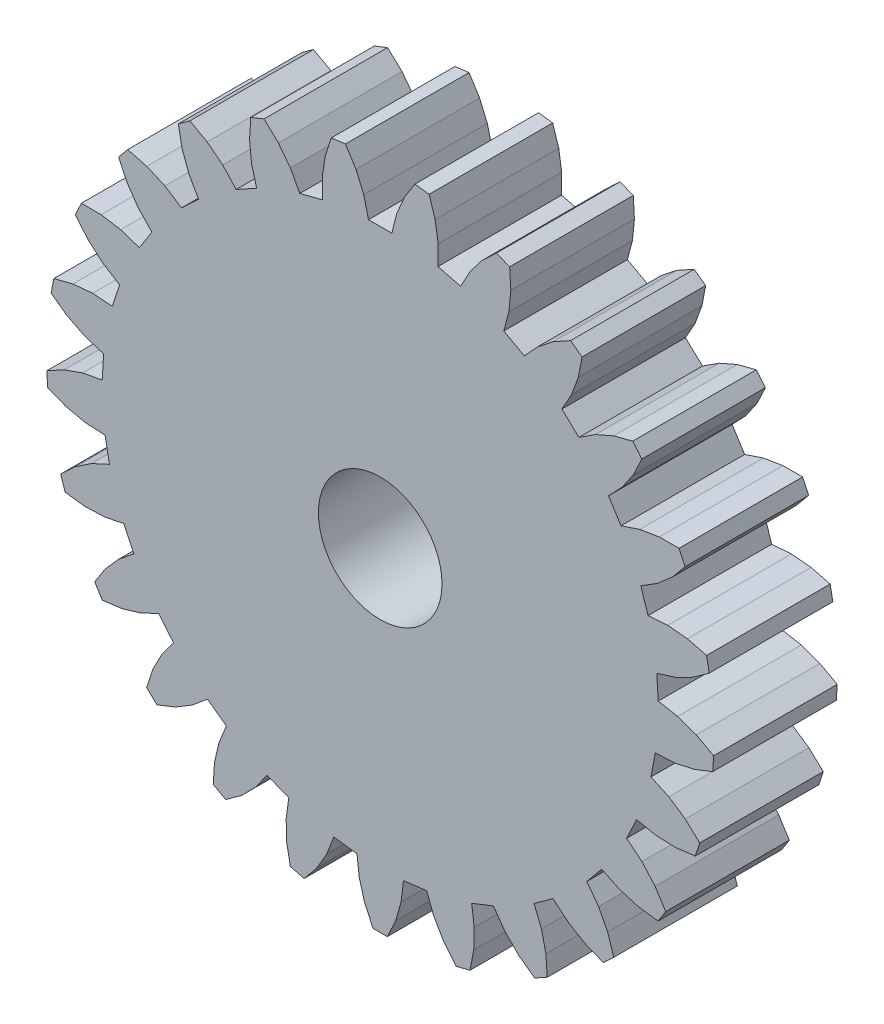
SolidWorks part; units mm, degrees
ref_plane "Front Plane" through (0, 0, 0) normal (0, 0, 1) x (1, 0, 0)
ref_plane "Top Plane" through (0, 0, 0) normal (0, 1, 0) x (1, 0, 0)
ref_plane "Right Plane" through (0, 0, 0) normal (1, 0, 0) x (0, 0, -1)
sketch "Sketch3" plane through (0, 0, 0) normal (0, 0, 1) x (1, 0, 0)
  line L0 (-2.8117, 26.9235) -> (-3.9548, 26.7791)
  line L1 (-3.9548, 26.7791) -> (-4.4453, 25.2575)
  line L2 (-4.4453, 25.2575) -> (-4.6871, 23.6772)
  line L3 (-4.6871, 23.6772) -> (-4.6739, 22.0785)
  line L5 (-0.9462, 22.5494) -> (-1.331, 24.1011)
  line L6 (-1.331, 24.1011) -> (-1.9582, 25.5717)
  line L7 (-1.9582, 25.5717) -> (-2.8117, 26.9235)
  line L8 (-9.4015, 25.3807) -> (-10.4728, 24.9565)
  line L9 (-10.4728, 24.9565) -> (-10.5694, 23.3607)
  line L10 (-10.5694, 23.3607) -> (-10.4106, 21.7699)
  line L11 (-10.4106, 21.7699) -> (-10.0003, 20.2247)
  line L13 (-6.5068, 21.6079) -> (-7.2654, 23.0152)
  line L14 (-7.2654, 23.0152) -> (-8.2386, 24.2836)
  line L15 (-8.2386, 24.2836) -> (-9.4015, 25.3807)
  line L16 (-15.4005, 22.2474) -> (-16.3327, 21.5702)
  line L17 (-16.3327, 21.5702) -> (-16.0295, 20.0005)
  line L18 (-16.0295, 20.0005) -> (-15.48, 18.4992)
  line L19 (-15.48, 18.4992) -> (-14.6983, 17.1046)
  line L21 (-11.6585, 19.3131) -> (-12.7433, 20.4875)
  line L22 (-12.7433, 20.4875) -> (-14.0013, 21.474)
  line L23 (-14.0013, 21.474) -> (-15.4005, 22.2474)
  line L24 (-16.0777, 15.8092) -> (-17.4205, 16.6769)
  line L25 (-17.4205, 16.6769) -> (-18.8844, 17.3196)
  line L26 (-18.8844, 17.3196) -> (-20.4319, 17.7207)
  line L27 (-20.4319, 17.7207) -> (-21.1663, 16.833)
  line L28 (-21.1663, 16.833) -> (-20.4823, 15.388)
  line L29 (-20.4823, 15.388) -> (-19.5767, 14.0705)
  line L30 (-19.5767, 14.0705) -> (-18.4728, 12.9141)
  line L32 (-19.4867, 11.3164) -> (-21.0031, 11.8229)
  line L33 (-21.0031, 11.8229) -> (-22.5808, 12.0813)
  line L34 (-22.5808, 12.0813) -> (-24.1795, 12.085)
  line L35 (-24.1795, 12.085) -> (-24.6701, 11.0425)
  line L36 (-24.6701, 11.0425) -> (-23.6482, 9.813)
  line L37 (-23.6482, 9.813) -> (-22.4434, 8.7621)
  line L38 (-22.4434, 8.7621) -> (-21.0865, 7.9166)
  line L40 (-21.6713, 6.1169) -> (-23.266, 6.2304)
  line L41 (-23.266, 6.2304) -> (-24.8584, 6.0884)
  line L42 (-24.8584, 6.0884) -> (-26.4078, 5.6944)
  line L43 (-26.4078, 5.6944) -> (-26.6237, 4.5626)
  line L44 (-26.6237, 4.5626) -> (-25.3281, 3.6259)
  line L45 (-25.3281, 3.6259) -> (-23.8998, 2.9076)
  line L46 (-23.8998, 2.9076) -> (-22.3754, 2.4261)
  line L48 (-22.4942, 0.5375) -> (-24.067, 0.2509)
  line L49 (-24.067, 0.2509) -> (-25.574, -0.2827)
  line L50 (-25.574, -0.2827) -> (-26.9768, -1.0497)
  line L51 (-26.9768, -1.0497) -> (-26.9044, -2.1996)
  line L52 (-26.9044, -2.1996) -> (-25.4166, -2.7847)
  line L53 (-25.4166, -2.7847) -> (-23.8546, -3.1252)
  line L54 (-23.8546, -3.1252) -> (-22.2582, -3.2124)
  line L56 (-21.9036, -5.0712) -> (-23.3558, -5.74)
  line L57 (-23.3558, -5.74) -> (-24.6828, -6.6316)
  line L58 (-24.6828, -6.6316) -> (-25.8507, -7.7233)
  line L59 (-25.8507, -7.7233) -> (-25.4947, -8.8191)
  line L60 (-25.4947, -8.8191) -> (-23.9081, -9.0158)
  line L61 (-23.9081, -9.0158) -> (-22.3104, -8.9572)
  line L62 (-22.3104, -8.9572) -> (-20.7426, -8.6447)
  line L64 (-19.9368, -10.3569) -> (-21.177, -11.3658)
  line L65 (-21.177, -11.3658) -> (-22.2406, -12.5594)
  line L66 (-22.2406, -12.5594) -> (-23.1004, -13.9073)
  line L67 (-23.1004, -13.9073) -> (-22.483, -14.8801)
  line L68 (-22.483, -14.8801) -> (-20.8973, -14.6761)
  line L69 (-20.8973, -14.6761) -> (-19.3645, -14.222)
  line L70 (-19.3645, -14.222) -> (-17.9236, -13.5294)
  line L72 (-16.7174, -14.9874) -> (-17.6677, -16.273)
  line L73 (-17.6677, -16.273) -> (-18.401, -17.6937)
  line L74 (-18.401, -17.6937) -> (-18.8985, -19.213)
  line L75 (-18.8985, -19.213) -> (-18.0586, -20.0017)
  line L76 (-18.0586, -20.0017) -> (-16.5735, -19.4098)
  line L77 (-16.5735, -19.4098) -> (-15.2017, -18.5887)
  line L78 (-15.2017, -18.5887) -> (-13.9783, -17.5595)
  line L80 (-12.4474, -18.6718) -> (-13.0482, -20.1533)
  line L81 (-13.0482, -20.1533) -> (-13.4052, -21.7117)
  line L82 (-13.4052, -21.7117) -> (-13.5092, -23.307)
  line L83 (-13.5092, -23.307) -> (-12.4996, -23.8621)
  line L84 (-12.4996, -23.8621) -> (-11.2083, -22.9194)
  line L85 (-11.2083, -22.9194) -> (-10.0838, -21.783)
  line L86 (-10.0838, -21.783) -> (-9.1548, -20.4819)
  line L88 (-7.3954, -21.1785) -> (-7.6088, -22.7629)
  line L89 (-7.6088, -22.7629) -> (-7.5671, -24.3611)
  line L90 (-7.5671, -24.3611) -> (-7.2711, -25.9322)
  line L91 (-7.2711, -25.9322) -> (-6.1551, -26.2187)
  line L92 (-6.1551, -26.2187) -> (-5.1389, -24.9846)
  line L93 (-5.1389, -24.9846) -> (-4.3324, -23.6042)
  line L94 (-4.3324, -23.6042) -> (-3.7561, -22.1129)
  line L96 (-1.8787, -22.3501) -> (-1.6914, -23.9378)
  line L97 (-1.6914, -23.9378) -> (-1.2535, -25.4754)
  line L98 (-1.2535, -25.4754) -> (-0.5761, -26.9235)
  line L99 (-0.5761, -26.9235) -> (0.5761, -26.9235)
  line L100 (0.5761, -26.9235) -> (1.2534, -25.4754)
  line L101 (1.2534, -25.4754) -> (1.6914, -23.9378)
  line L102 (1.6914, -23.9378) -> (1.8787, -22.3501)
  line L104 (3.7561, -22.1129) -> (4.3323, -23.6042)
  line L105 (4.3323, -23.6042) -> (5.1389, -24.9846)
  line L106 (5.1389, -24.9846) -> (6.1551, -26.2187)
  line L107 (6.1551, -26.2187) -> (7.2711, -25.9322)
  line L108 (7.2711, -25.9322) -> (7.567, -24.3611)
  line L109 (7.567, -24.3611) -> (7.6088, -22.7629)
  line L110 (7.6088, -22.7629) -> (7.3954, -21.1785)
  line L112 (9.1548, -20.4819) -> (10.0838, -21.783)
  line L113 (10.0838, -21.783) -> (11.2083, -22.9194)
  line L114 (11.2083, -22.9194) -> (12.4995, -23.8621)
  line L115 (12.4995, -23.8621) -> (13.5092, -23.307)
  line L116 (13.5092, -23.307) -> (13.4051, -21.7117)
  line L117 (13.4051, -21.7117) -> (13.0482, -20.1533)
  line L118 (13.0482, -20.1533) -> (12.4474, -18.6718)
  line L120 (13.9783, -17.5595) -> (15.2017, -18.5887)
  line L121 (15.2017, -18.5887) -> (16.5735, -19.4098)
  line L122 (16.5735, -19.4098) -> (18.0586, -20.0017)
  line L123 (18.0586, -20.0017) -> (18.8985, -19.213)
  line L124 (18.8985, -19.213) -> (18.401, -17.6937)
  line L125 (18.401, -17.6937) -> (17.6676, -16.273)
  line L126 (17.6676, -16.273) -> (16.7173, -14.9874)
  line L128 (17.9235, -13.5294) -> (19.3645, -14.222)
  line L129 (19.3645, -14.222) -> (20.8973, -14.6761)
  line L130 (20.8973, -14.6761) -> (22.483, -14.8801)
  line L131 (22.483, -14.8801) -> (23.1003, -13.9073)
  line L132 (23.1003, -13.9073) -> (22.2406, -12.5594)
  line L133 (22.2406, -12.5594) -> (21.177, -11.3658)
  line L134 (21.177, -11.3658) -> (19.9368, -10.3569)
  line L136 (20.7425, -8.6447) -> (22.3104, -8.9572)
  line L137 (22.3104, -8.9572) -> (23.9081, -9.0158)
  line L138 (23.9081, -9.0158) -> (25.4946, -8.8191)
  line L139 (25.4946, -8.8191) -> (25.8507, -7.7233)
  line L140 (25.8507, -7.7233) -> (24.6828, -6.6316)
  line L141 (24.6828, -6.6316) -> (23.3558, -5.74)
  line L142 (23.3558, -5.74) -> (21.9036, -5.0712)
  line L144 (22.2582, -3.2124) -> (23.8545, -3.1252)
  line L145 (23.8545, -3.1252) -> (25.4166, -2.7847)
  line L146 (25.4166, -2.7847) -> (26.9044, -2.1996)
  line L147 (26.9044, -2.1996) -> (26.9768, -1.0497)
  line L148 (26.9768, -1.0497) -> (25.574, -0.2827)
  line L149 (25.574, -0.2827) -> (24.067, 0.2509)
  line L150 (24.067, 0.2509) -> (22.4941, 0.5375)
  line L152 (22.3753, 2.4261) -> (23.8998, 2.9076)
  line L153 (23.8998, 2.9076) -> (25.3281, 3.6259)
  line L154 (25.3281, 3.6259) -> (26.6236, 4.5626)
  line L155 (26.6236, 4.5626) -> (26.4078, 5.6944)
  line L156 (26.4078, 5.6944) -> (24.8584, 6.0884)
  line L157 (24.8584, 6.0884) -> (23.2659, 6.2304)
  line L158 (23.2659, 6.2304) -> (21.6712, 6.1169)
  line L160 (21.0865, 7.9166) -> (22.4433, 8.7621)
  line L161 (22.4433, 8.7621) -> (23.6481, 9.813)
  line L162 (23.6481, 9.813) -> (24.6701, 11.0425)
  line L163 (24.6701, 11.0425) -> (24.1795, 12.085)
  line L164 (24.1795, 12.085) -> (22.5807, 12.0813)
  line L165 (22.5807, 12.0813) -> (21.003, 11.8229)
  line L166 (21.003, 11.8229) -> (19.4867, 11.3164)
  line L168 (18.4727, 12.9141) -> (19.5767, 14.0705)
  line L169 (19.5767, 14.0705) -> (20.4823, 15.388)
  line L170 (20.4823, 15.388) -> (21.1663, 16.833)
  line L171 (21.1663, 16.833) -> (20.4319, 17.7207)
  line L172 (20.4319, 17.7207) -> (18.8843, 17.3196)
  line L173 (18.8843, 17.3196) -> (17.4205, 16.6769)
  line L174 (17.4205, 16.6769) -> (16.0777, 15.8092)
  line L176 (18.4727, 12.9141) -> (19.4867, 11.3164)
  line L177 (14.6983, 17.1046) -> (15.48, 18.4992)
  line L178 (15.48, 18.4992) -> (16.0295, 20.0005)
  line L179 (16.0295, 20.0005) -> (16.3327, 21.5702)
  line L180 (16.3327, 21.5702) -> (15.4005, 22.2474)
  line L181 (15.4005, 22.2474) -> (14.0013, 21.474)
  line L182 (14.0013, 21.474) -> (12.7433, 20.4875)
  line L183 (12.7433, 20.4875) -> (11.6585, 19.3131)
  line L185 (10.0003, 20.2247) -> (10.4106, 21.7699)
  line L186 (10.4106, 21.7699) -> (10.5694, 23.3607)
  line L187 (10.5694, 23.3607) -> (10.4727, 24.9565)
  line L188 (10.4727, 24.9565) -> (9.4014, 25.3807)
  line L189 (9.4014, 25.3807) -> (8.2386, 24.2836)
  line L190 (8.2386, 24.2836) -> (7.2654, 23.0152)
  line L191 (7.2654, 23.0152) -> (6.5067, 21.6079)
  line L193 (4.6739, 22.0785) -> (4.6871, 23.6772)
  line L194 (4.6871, 23.6772) -> (4.4453, 25.2575)
  line L195 (4.4453, 25.2575) -> (3.9548, 26.7791)
  line L196 (3.9548, 26.7791) -> (2.8117, 26.9235)
  line L197 (2.8117, 26.9235) -> (1.9581, 25.5717)
  line L198 (1.9581, 25.5717) -> (1.3309, 24.1011)
  line L199 (1.3309, 24.1011) -> (0.9462, 22.5494)
  line L201 (-6.5068, 21.6079) -> (-4.6739, 22.0785)
  line L202 (-0.9462, 22.5494) -> (0.9462, 22.5494)
  line L203 (4.6739, 22.0785) -> (6.5067, 21.6079)
  line L204 (10.0003, 20.2247) -> (11.6585, 19.3131)
  line L205 (14.6983, 17.1046) -> (16.0777, 15.8092)
  line L206 (21.0865, 7.9166) -> (21.6712, 6.1169)
  line L207 (22.3753, 2.4261) -> (22.4941, 0.5375)
  line L208 (22.2582, -3.2124) -> (21.9036, -5.0712)
  line L209 (20.7425, -8.6447) -> (19.9368, -10.3569)
  line L210 (17.9235, -13.5294) -> (16.7173, -14.9874)
  line L211 (13.9783, -17.5595) -> (12.4474, -18.6718)
  line L212 (9.1548, -20.4819) -> (7.3954, -21.1785)
  line L213 (3.7561, -22.1129) -> (1.8787, -22.3501)
  line L214 (-1.8787, -22.3501) -> (-3.7561, -22.1129)
  line L215 (-7.3954, -21.1785) -> (-9.1548, -20.4819)
  line L216 (-12.4474, -18.6718) -> (-13.9783, -17.5595)
  line L217 (-16.7174, -14.9874) -> (-17.9236, -13.5294)
  line L218 (-19.9368, -10.3569) -> (-20.7426, -8.6447)
  line L219 (-21.9036, -5.0712) -> (-22.2582, -3.2124)
  line L220 (-22.4942, 0.5375) -> (-22.3754, 2.4261)
  line L221 (-21.6713, 6.1169) -> (-21.0865, 7.9166)
  line L222 (-19.4867, 11.3164) -> (-18.4728, 12.9141)
  line L223 (-16.0777, 15.8092) -> (-14.6983, 17.1046)
  line L224 (-11.6585, 19.3131) -> (-10.0003, 20.2247)
  circle A0 centre (0, 0) radius 5
extrude "Boss-Extrude1" add sketch "Sketch3" along normal blind 10
sketch "Sketch4" plane through (0, 0, 0) normal (0, 0, -1) x (-1, 0, 0)
  circle A0 centre (0, 0) radius 5
  circle A1 centre (0, 0) radius 10
extrude "Boss-Extrude2" add sketch "Sketch4" along normal blind 3
fillet "Fillet6" radius 5.5 1 edges at (-10, 0, -3)
